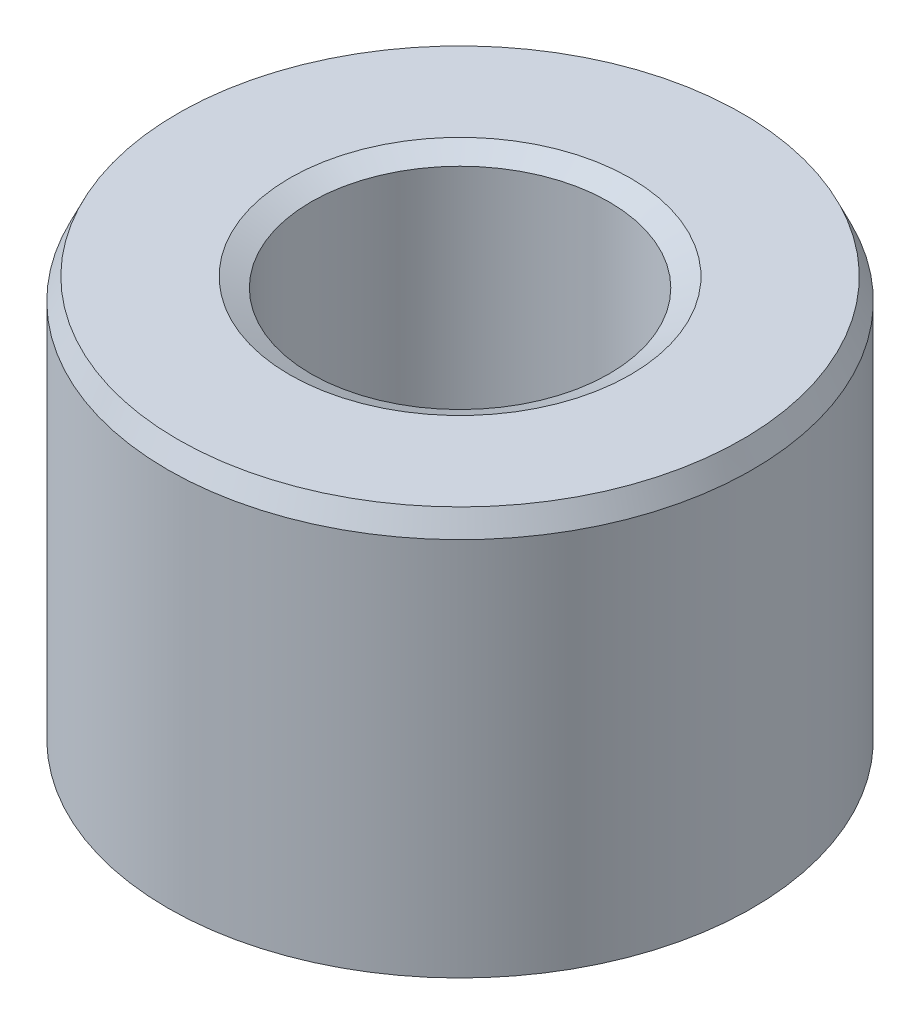
SolidWorks part; units mm, degrees
ref_plane "Front Plane" through (0, 0, 0) normal (0, 0, 1) x (1, 0, 0)
ref_plane "Top Plane" through (0, 0, 0) normal (0, 1, 0) x (1, 0, 0)
ref_plane "Right Plane" through (0, 0, 0) normal (1, 0, 0) x (0, 0, -1)
sketch "Sketch1" plane through (0, 0, 0) normal (0, 1, 0) x (1, 0, 0)
  circle A0 centre (0, 0) radius 45
  dimension "SLEEVE_OD" = 90
extrude "Boss-Extrude1" add sketch "Sketch1" along normal blind 63.2652
sketch "Sketch2" plane through (0, 0, 0) normal (0, 1, 0) x (1, 0, 0)
  circle A0 centre (0, 0) radius 22.9476
  dimension "BORE_D" = 45.8952
extrude "Cut-Extrude1" cut sketch "Sketch2" along normal through all
chamfer "Chamfer1" distance 3.2868 angle 24.928 4 edges at (0, 63.2652, 22.9476) (0, 0, 22.9476) (0, 0, 45) (0, 63.2652, 45) first distance on face at (0, 63.2652, 22.9476) first distance on face at (0, 0, 22.9476) first distance on face at (0, 63.2652, 45)
